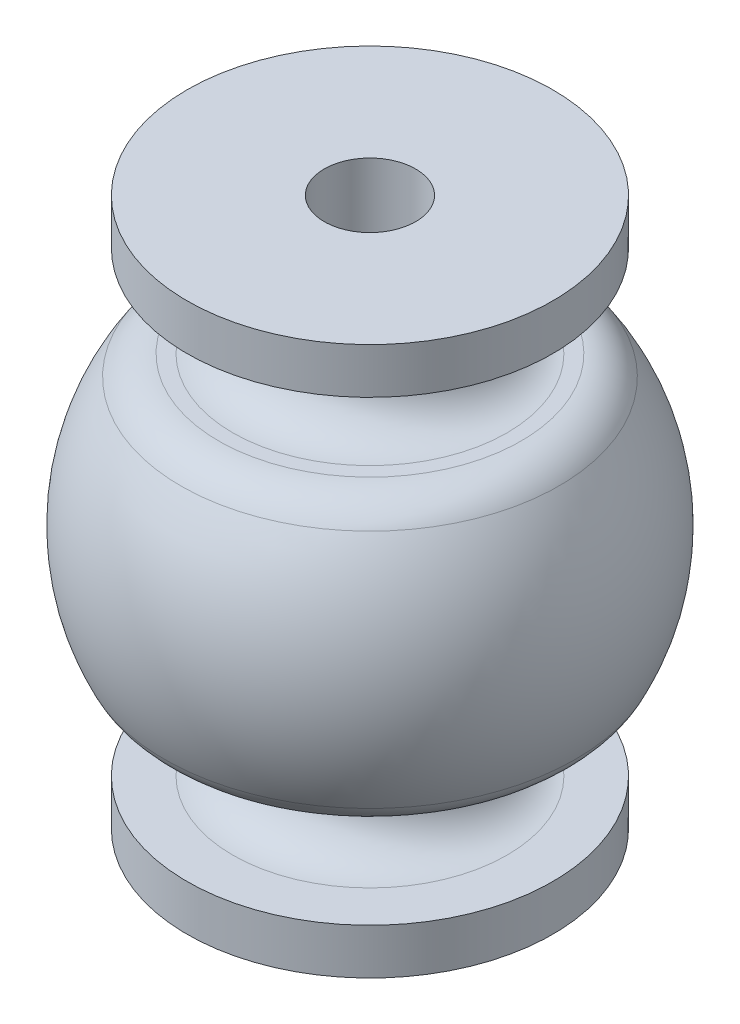
SolidWorks part; units mm, degrees
ref_plane "Front Plane" through (0, 0, 0) normal (0, 0, 1) x (1, 0, 0)
ref_plane "Top Plane" through (0, 0, 0) normal (0, 1, 0) x (1, 0, 0)
ref_plane "Right Plane" through (0, 0, 0) normal (1, 0, 0) x (0, 0, -1)
sketch "Sketch1" plane through (0, 0, 0) normal (0, 0, 1) x (1, 0, 0)
  line L0 (0, 6) -> (0, -6)
  line L1 (0, 6) -> (-4, 6)
  line L2 (0, 6) -> (-2, 6)
  line L3 (-2, 6) -> (-2, 3)
  line L4 (-4, 6) -> (0, 6)
  line L5 (-4, 6) -> (-4, 5)
  line L6 (-4, 5) -> (0, 5)
  line L7 (0, 6) -> (0, 5)
  line L8 (-2, 3) -> (-3.802, 3)
  line L9 (0, 0) -> (-4.9939, 0)
  line L10 (0, 5) -> (-1, 5)
  line L11 (-1, 6) -> (-1, 2)
  line L12 (-1, 2) -> (-4.4665, 2)
  line L13 (-4, -5) -> (0, -5)
  line L14 (0, -6) -> (0, -5)
  line L15 (-4, -6) -> (0, -6)
  line L16 (-4, -6) -> (-4, -5)
  line L17 (-2, -6) -> (-2, -3)
  line L18 (-2, -3) -> (-4.174, -3)
  line L19 (-1, -6) -> (-1, -2)
  line L20 (-1, -2) -> (-4.6827, -2)
  line L21 (-1, 2) -> (-3.802, 2) construction
  line L22 (-1, 5) -> (-1, 2) construction
  circle A0 centre (0, -0.2472) radius 5
  circle A1 centre (0, -0.2472) radius 4
  point P4 (0, 0)
  dimension "D5" = 10
  dimension "D1" = 12
  dimension "D2" = 4
  dimension "D3" = 2
  dimension "D4" = 1
  dimension "D6" = 2
  dimension "D7" = 1
revolve "Revolve1" add sketch "Sketch1" angle 360 about L0 region at (-1.5, 5.5, 0) region at (-1.554, 4.7478, 0) region at (-3, 5.5, 0) region at (-1.5072, 3.9777, 0) region at (-1.8573, 2.6078, 0) region at (-4.3935, -1.0135, 0) region at (-4.2706, 1.0237, 0) region at (-1.5141, -5.5204, 0) region at (-3.5054, 2.5195, 0) region at (-1.9512, -2.7678, 0) region at (-1.5206, -4.4475, 0) region at (-3.8615, -2.513, 0) region at (-1.8546, -4.9446, 0) region at (-3, -5.5, 0)
fillet "Fillet1" radius 1 6 edges at (-2, -5, 0) (-2, -3, 0) (-4.174, -3, 0) (-3.802, 3, 0) (-2, 3, 0) (-2, 5, 0)
